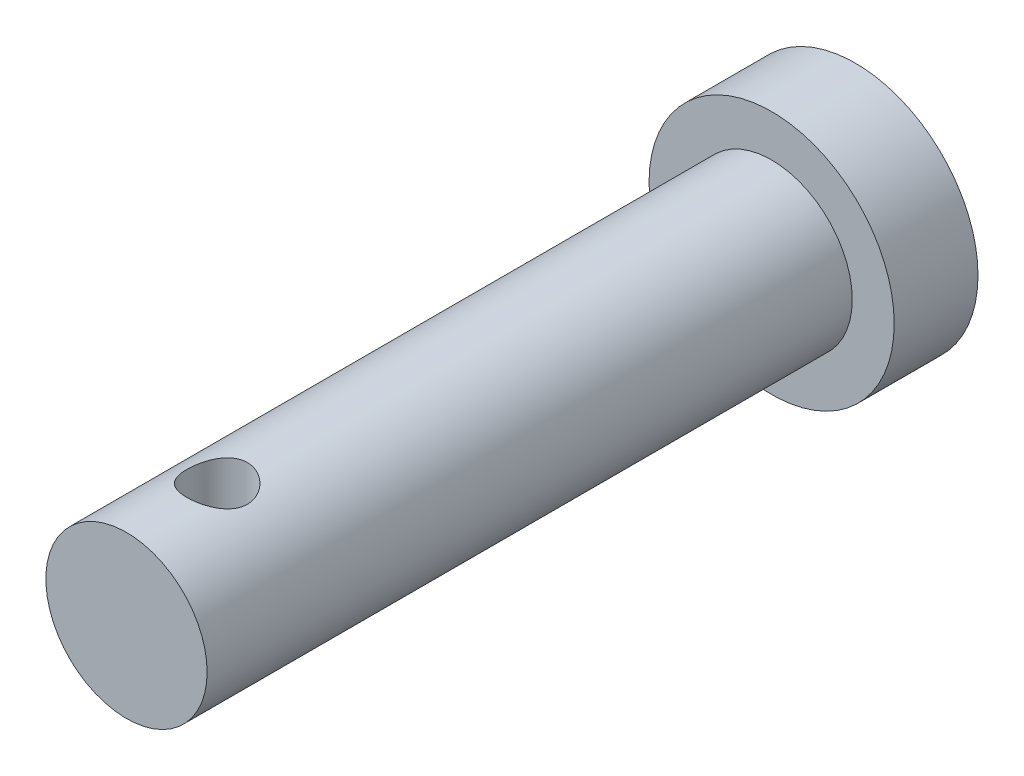
SolidWorks part; units mm, degrees
ref_plane "Front Plane" through (0, 0, 0) normal (0, 0, 1) x (1, 0, 0)
ref_plane "Top Plane" through (0, 0, 0) normal (0, 1, 0) x (1, 0, 0)
ref_plane "Right Plane" through (0, 0, 0) normal (1, 0, 0) x (0, 0, -1)
sketch "Sketch1" plane through (0, 0, 0) normal (0, 0, 1) x (1, 0, 0)
  circle A0 centre (0, 0) radius 4.826
  dimension "D1" = 9.652
extrude "Boss-Extrude1" add sketch "Sketch1" along normal blind 3.3
sketch "Sketch2" plane through (0, 0, 3.3) normal (0, 0, 1) x (1, 0, 0)
  circle A0 centre (0, 0) radius 3.175
  dimension "D1" = 6.35
extrude "Boss-Extrude2" add sketch "Sketch2" along normal blind 25.4
sketch "Sketch3" plane through (0, 0, 0) normal (0, 1, 0) x (1, 0, 0)
  line L0 (-3.175, -28.7) -> (3.175, -28.7) construction
  circle A0 centre (0, -25.13) radius 1.1906
  dimension "D1" = 2.3813
  dimension "D2" = 3.57
extrude "Cut-Extrude1" cut sketch "Sketch3" against normal blind 10 and the other way blind 10
